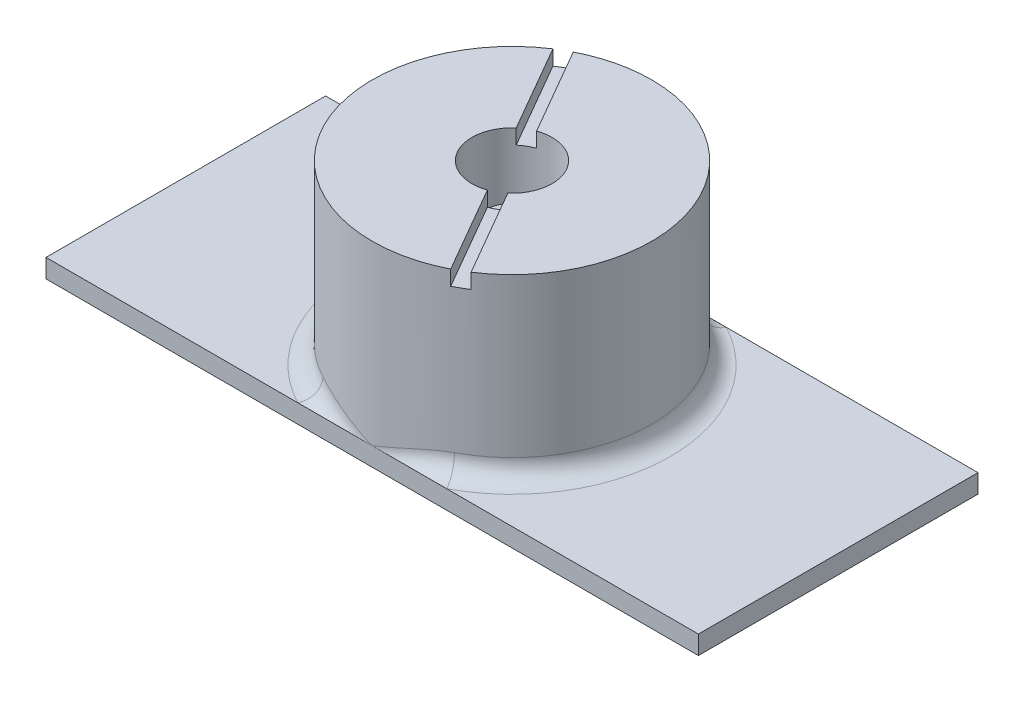
SolidWorks part; units mm, degrees
ref_plane "Front Plane" through (0, 0, 0) normal (0, 0, 1) x (1, 0, 0)
ref_plane "Top Plane" through (0, 0, 0) normal (0, 1, 0) x (1, 0, 0)
ref_plane "Right Plane" through (0, 0, 0) normal (1, 0, 0) x (0, 0, -1)
sketch "Sketch1" plane through (0, 0, 0) normal (0, 1, 0) x (1, 0, 0)
  circle A0 centre (0, 0) radius 15
  dimension "D1" = 30
extrude "Boss-Extrude1" add sketch "Sketch1" along normal blind 10
sketch "Sketch2" plane through (0, 10, 0) normal (0, 1, 0) x (1, 0, 0)
  circle A0 centre (0, 0) radius 2.85
  dimension "D1" = 5.7
extrude "Boss-Extrude2" add sketch "Sketch2" along normal blind 3
sketch "Sketch3" plane through (0, 10, 0) normal (0, 1, 0) x (1, 0, 0)
  line L1 (-14.9908, 0.525) -> (14.9908, 0.525)
  line L2 (-14.9908, 0.525) -> (-14.9908, -0.525) construction
  line L3 (-14.9908, -0.525) -> (14.9908, -0.525)
  line L4 (14.9908, 0.525) -> (14.9908, -0.525) construction
  line L5 (-14.9908, 0.525) -> (14.9908, -0.525) construction
  line L6 (-14.9908, -0.525) -> (14.9908, 0.525) construction
  arc A0 (14.9908, 0.525) -> (-14.9908, 0.525) centre (0, 0) ccw construction
  circle A1 centre (0, 0) radius 15
  arc A2 (-14.9908, 0.525) -> (-14.9908, -0.525) centre (0, 0) ccw
  arc A3 (-14.9908, -0.525) -> (14.9908, -0.525) centre (0, 0) ccw construction
  arc A4 (14.9908, -0.525) -> (14.9908, 0.525) centre (0, 0) ccw
  point P0 (0, 0)
  point P5 (0, 0)
  dimension "D1" = 0
  dimension "D2" = 1.05
extrude "Boss-Extrude3" add sketch "Sketch3" along normal blind 1
sketch "Sketch4" plane through (0, 10, 0) normal (0, 1, 0) x (1, 0, 0)
  circle A0 centre (0, 0) radius 4.3
  arc A1 (-14.9908, -0.525) -> (14.9908, -0.525) centre (0, 0) ccw construction
  circle A2 centre (0, 0) radius 15
  point P3 (5.977, -0.4055)
  dimension "D1" = 8.6
extrude "Boss-Extrude4" add sketch "Sketch4" along normal blind 9
sketch "Sketch6" plane through (0, 19, 0) normal (0, 1, 0) x (1, 0, 0)
  line L0 (-7.5, 12.9904) -> (7.5, -12.9904)
  circle A0 centre (0, 0) radius 15 construction
  point P7 (0, 0)
  dimension "D1" = 30
extrude "Cut-Extrude-Thin1" cut sketch "Sketch6" against normal blind 1.6 and the other way through all thin thin type mid plane wall 1.6
sketch "Sketch8" plane through (0, 0, 0) normal (0, -1, 0) x (-1, 0, 0)
  line L1 (35, -15) -> (-35, -15)
  line L2 (35, -15) -> (35, 15)
  line L3 (35, 15) -> (-35, 15)
  line L4 (-35, -15) -> (-35, 15)
  line L5 (35, -15) -> (-35, 15) construction
  line L6 (35, 15) -> (-35, -15) construction
  point P0 (0, 0)
  dimension "D1" = 70
  dimension "D2" = 30
extrude "Boss-Extrude5" add sketch "Sketch8" along normal blind 2
fillet "Fillet1" radius 2 2 edges at (15, 0, 0) (-15, 0, 0)
